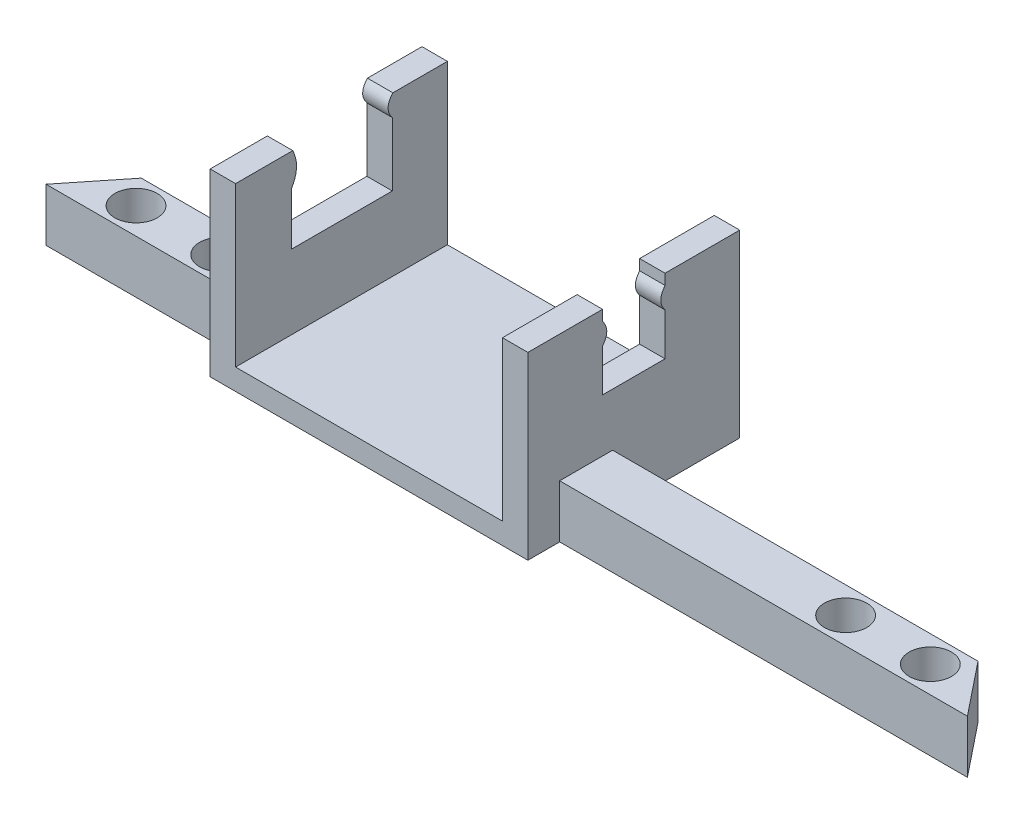
SolidWorks part; units mm, degrees
ref_plane "前视基准面" through (0, 0, 0) normal (0, 0, 1) x (1, 0, 0)
ref_plane "上视基准面" through (0, 0, 0) normal (0, 1, 0) x (1, 0, 0)
ref_plane "右视基准面" through (0, 0, 0) normal (1, 0, 0) x (0, 0, -1)
sketch "草图1" plane through (0, 0, 0) normal (0, 1, 0) x (1, 0, 0)
  line L1 (-15, 10) -> (15, 10)
  line L2 (-15, 10) -> (-15, -10)
  line L3 (-15, -10) -> (15, -10)
  line L4 (15, 10) -> (15, -10)
  line L5 (-15, 10) -> (15, -10) construction
  line L6 (-15, -10) -> (15, 10) construction
  point P0 (0, 0)
  dimension "D1" = 30
  dimension "D2" = 20
extrude "凸台-拉伸1" add sketch "草图1" along normal blind 2
sketch "草图2" plane through (-15, 0, 0) normal (-1, 0, 0) x (0, 0, 1)
  line L0 (-10, 2) -> (10, 2)
  line L1 (-10, 2) -> (-10, 17)
  line L2 (10, 2) -> (10, 17)
  line L3 (-10, 17) -> (-4.85, 17)
  line L4 (-4.8, 15.0006) -> (-4.8, 9.0002)
  line L5 (-4.8, 9.0002) -> (4.7, 9.0002)
  line L6 (4.7, 9.0002) -> (4.7, 14)
  line L7 (4.6, 17) -> (10, 17)
  spline S0 degree 2 poles (-4.85, 17) (-3.9754, 16.0184) (-4.8, 15.0006) knots 0 0 0 1 1 1
  spline S1 degree 2 poles (4.6, 17) (3.8446, 15.4063) (4.7, 14) knots 0 0 0 1 1 1
  point P8 (-4.4, 16.0006)
  point P11 (-4.8, 15.0006)
  point P13 (4.3, 15)
  point P14 (4.7, 14)
  dimension "D1" = 15
  dimension "D2" = 8
  dimension "D3" = 5.15
  dimension "D4" = 9.5
  dimension "D5" = 2
  dimension "D6" = 0.4
  dimension "D7" = 1
  dimension "D8" = 0.4
extrude "凸台-拉伸2" add sketch "草图2" against normal blind 2.4 separate body
sketch "草图3" plane through (15, 0, 0) normal (1, 0, 0) x (0, 0, -1)
  line L0 (-10, 2) -> (10, 2)
  line L1 (-10, 2) -> (-10, 17)
  line L2 (10, 2) -> (10, 17)
  line L3 (-10, 17) -> (-2.95, 17)
  line L4 (-2.95, 17) -> (-2.95, 16)
  line L5 (-2.95, 10) -> (2.95, 10)
  line L6 (2.95, 10) -> (2.95, 14)
  line L7 (2.95, 17) -> (10, 17)
  line L8 (-2.95, 14) -> (-2.95, 10)
  line L9 (2.95, 16) -> (2.95, 17)
  spline S0 degree 2 poles (-2.95, 16) (-2.15, 15) (-2.95, 14) knots 0 0 0 1 1 1
  spline S1 degree 2 poles (2.95, 16) (2.15, 15) (2.95, 14) knots 0 0 0 1 1 1
  point P10 (-2.95, 16)
  point P11 (-2.55, 15)
  point P12 (-2.95, 14)
  point P15 (2.95, 16)
  point P17 (2.55, 15)
  point P18 (2.95, 14)
  dimension "D1" = 15
  dimension "D2" = 7
  dimension "D3" = 5.9
  dimension "D4" = 7.05
  dimension "D5" = 0.4
  dimension "D6" = 4
  dimension "D7" = 5
  dimension "D8" = 6
  dimension "D9" = 0.4
  dimension "D10" = 4
  dimension "D11" = 5
  dimension "D12" = 6
extrude "凸台-拉伸3" add sketch "草图3" against normal blind 2.4
sketch "草图4" plane through (0, 0, 0) normal (0, -1, 0) x (1, 0, 0)
  line L0 (10, 0.0806) -> (10, -11.5199) construction
  line L1 (-29.5, 2) -> (49.5, 2)
  line L2 (-33.5, 7) -> (53.5, 7)
  line L3 (-29.5, 2) -> (-33.5, 7)
  line L4 (49.5, 2) -> (53.5, 7)
  line L6 (-15, 10) -> (12.6, 10) construction
  circle A0 centre (-27.5, 4.5) radius 2
  circle A1 centre (47.5, 4.5) radius 2
  circle A2 centre (-19.5, 4.5) radius 2
  circle A3 centre (39.5, 4.5) radius 2
  point P4 (10, 2)
  point P8 (10, 7)
  dimension "D5" = 4
  dimension "D6" = 2.5
  dimension "D11" = 4
  dimension "D13" = 4
  dimension "D1" = 79
  dimension "D2" = 87
  dimension "D3" = 3
  dimension "D4" = 5
  dimension "D7" = 6
  dimension "D8" = 2.5
  dimension "D9" = 75
  dimension "D10" = 10
  dimension "D12" = 8
  dimension "D14" = 8
extrude "凸台-拉伸4" add sketch "草图4" against normal blind 5
sketch "草图5" plane through (0, 5, 0) normal (0, 1, 0) x (1, 0, 0)
  line L4 (-12.6, -7) -> (12.6, -7)
  line L5 (12.6, -7) -> (12.6, -2)
  line L6 (12.6, -2) -> (-12.6, -2)
  line L7 (-12.6, -2) -> (-12.6, -7)
  line L8 (-12.6, -7) -> (12.6, -7)
  line L9 (12.6, -7) -> (12.6, -2)
  line L10 (12.6, -2) -> (-12.6, -2)
  line L11 (-12.6, -2) -> (-12.6, -7)
  dimension "D1" = 0
extrude "切除-拉伸1" cut sketch "草图5" against normal up to surface (3 mm away) up to face at (0, 2, -4)
